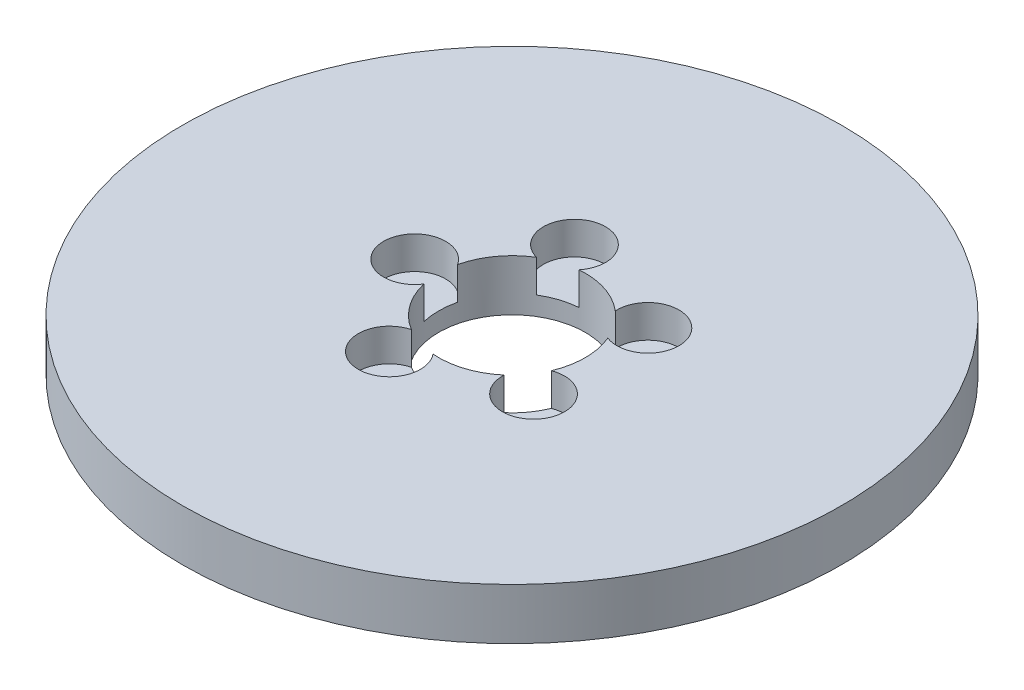
SolidWorks part; units mm, degrees
ref_plane "Front Plane" through (0, 0, 0) normal (0, 0, 1) x (1, 0, 0)
ref_plane "Top Plane" through (0, 0, 0) normal (0, 1, 0) x (1, 0, 0)
ref_plane "Right Plane" through (0, 0, 0) normal (1, 0, 0) x (0, 0, -1)
sketch "Sketch1" plane through (0, 0, 0) normal (0, 1, 0) x (1, 0, 0)
  circle A0 centre (0, 0) radius 45
  dimension "FLANGE_OD" = 90
extrude "Boss-Extrude1" add sketch "Sketch1" along normal blind 7
sketch "Sketch2" plane through (0, 0, 0) normal (0, 1, 0) x (1, 0, 0)
  circle A0 centre (0, 0) radius 10
  dimension "BORE_D" = 20
extrude "Cut-Extrude1" cut sketch "Sketch2" along normal through all
sketch "Sketch3" plane through (0, 7, 0) normal (0, 1, 0) x (1, 0, 0)
  circle A0 centre (0, 0) radius 13.2886 construction
  circle A1 centre (-13.2886, 0) radius 4.2382
  dimension "BOLT_D" = 8.4764
  dimension "BOLT_PCD" = 26.5772
extrude "Cut-Extrude2" cut sketch "Sketch3" against normal blind 4.4556
pattern_circular "CirPattern1" count 5 over 360 about axis through (0, 0, 0) along (0, 1, 0) of "Cut-Extrude2"
